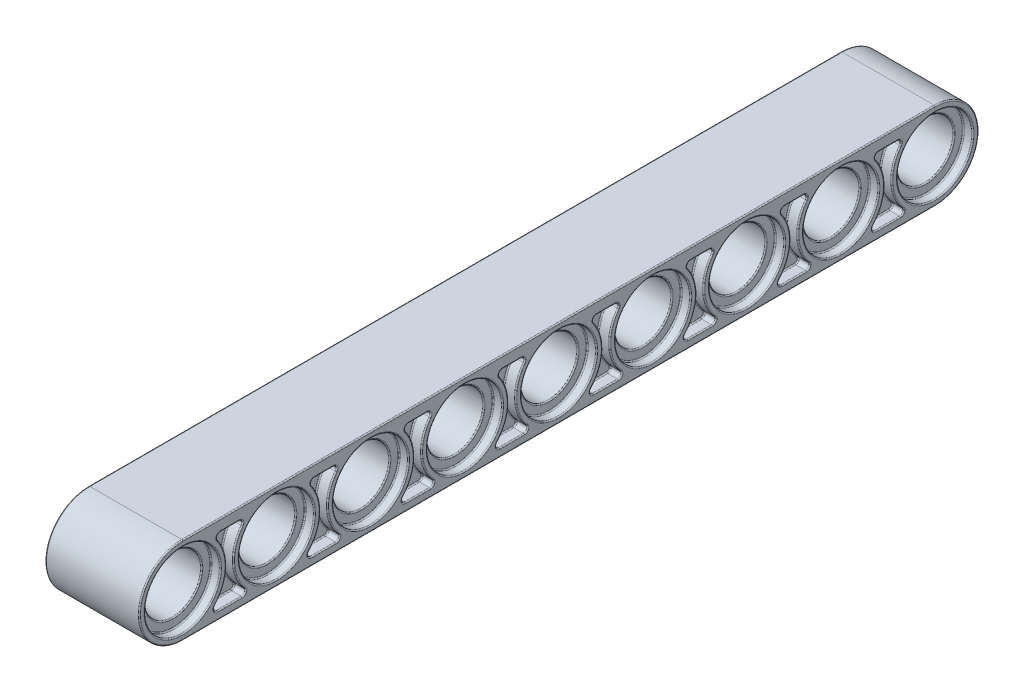
SolidWorks part; units mm, degrees
ref_plane "Front Plane" through (0, 0, 0) normal (0, 0, 1) x (1, 0, 0)
ref_plane "Top Plane" through (0, 0, 0) normal (0, 1, 0) x (1, 0, 0)
ref_plane "Right Plane" through (0, 0, 0) normal (1, 0, 0) x (0, 0, -1)
sketch "Sketch2" plane through (0, 0, 0) normal (1, 0, 0) x (0, 0, -1)
  line L0 (-40.2133, 0) -> (23.7867, 0) construction
  line L1 (-40.2133, 3.7) -> (23.7867, 3.7)
  line L2 (-40.2133, -3.7) -> (23.7867, -3.7)
  arc A0 (-40.2133, 3.7) -> (-40.2133, -3.7) centre (-40.2133, 0) ccw
  arc A1 (23.7867, -3.7) -> (23.7867, 3.7) centre (23.7867, 0) ccw
  circle A2 centre (-40.2133, 0) radius 2.4
  circle A3 centre (-32.2133, 0) radius 2.4
  circle A4 centre (-24.2133, 0) radius 2.4
  circle A5 centre (-16.2133, 0) radius 2.4
  circle A6 centre (-8.2133, 0) radius 2.4
  circle A7 centre (-0.2133, 0) radius 2.4
  circle A8 centre (7.7867, 0) radius 2.4
  circle A9 centre (15.7867, 0) radius 2.4
  circle A10 centre (23.7867, 0) radius 2.4
  point P3 (-8.2133, 0)
  dimension "D2" = 64
  dimension "D3" = 9
  dimension "D1" = 7.4
extrude "Boss-Extrude1" add sketch "Sketch2" along normal blind 8
sketch "Sketch3" plane through (8, 0, 0) normal (1, 0, 0) x (0, 0, -1)
  circle A0 centre (-40.2133, 0) radius 3.2
  circle A1 centre (-32.2133, 0) radius 3.2
  circle A2 centre (-24.2133, 0) radius 3.2
  circle A3 centre (-16.2133, 0) radius 3.2
  circle A4 centre (-8.2133, 0) radius 3.2
  circle A5 centre (-0.2133, 0) radius 3.2
  circle A6 centre (7.7867, 0) radius 3.2
  circle A7 centre (15.7867, 0) radius 3.2
  circle A8 centre (23.7867, 0) radius 3.2
  dimension "D1" = 6.4
  dimension "D2" = 9
extrude "Cut-Extrude1" cut sketch "Sketch3" against normal blind 0.8
ref_plane "Plane1" through (4, 0, 0) normal (1, 0, 0) x (0, 0, -1)
mirror "Mirror1" about plane through (4, 0, 0) normal (1, 0, 0) of "Cut-Extrude1"
sketch "Sketch4" plane through (8, 0, 0) normal (1, 0, 0) x (0, 0, -1)
  line L0 (-37.0133, 2.7) -> (-35.4133, 2.7)
  line L1 (23.7867, 3.7) -> (-40.2133, 3.7) construction
  line L2 (-40.2133, 0) -> (-51.0424, 0) construction
  line L3 (-37.2621, -3) -> (-35.1646, -3)
  line L4 (-29.0133, 2.7) -> (-27.4133, 2.7)
  line L5 (-29.2621, -3) -> (-27.1646, -3)
  line L6 (-21.0133, 2.7) -> (-19.4133, 2.7)
  line L7 (-21.2621, -3) -> (-19.1646, -3)
  line L8 (-13.0133, 2.7) -> (-11.4133, 2.7)
  line L9 (-13.2621, -3) -> (-11.1646, -3)
  line L10 (-5.0133, 2.7) -> (-3.4133, 2.7)
  line L11 (-5.2621, -3) -> (-3.1646, -3)
  line L12 (2.9867, 2.7) -> (4.5867, 2.7)
  line L13 (2.7379, -3) -> (4.8354, -3)
  line L14 (10.9867, 2.7) -> (12.5867, 2.7)
  line L15 (10.7379, -3) -> (12.8354, -3)
  line L16 (18.9867, 2.7) -> (20.5867, 2.7)
  line L17 (18.7379, -3) -> (20.8354, -3)
  line L20 (26.9867, 2.7) -> (28.5867, 2.7) [skipped]
  line L21 (26.7379, -3) -> (28.8354, -3) [skipped]
  arc A0 (-37.4834, -2.4975) -> (-37.2533, 2.22) centre (-40.2133, 0) ccw
  arc A1 (-35.1733, 2.22) -> (-34.9433, -2.4975) centre (-32.2133, 0) ccw
  arc A2 (-37.2621, -3) -> (-37.4834, -2.4975) centre (-37.2621, -2.7) cw
  arc A3 (-34.9433, -2.4975) -> (-35.1646, -3) centre (-35.1646, -2.7) cw
  arc A4 (-35.1733, 2.22) -> (-35.4133, 2.7) centre (-35.4133, 2.4) ccw
  arc A5 (-37.2533, 2.22) -> (-37.0133, 2.7) centre (-37.0133, 2.4) cw
  arc A6 (-29.2533, 2.22) -> (-29.0133, 2.7) centre (-29.0133, 2.4) cw
  arc A7 (-27.1733, 2.22) -> (-27.4133, 2.7) centre (-27.4133, 2.4) ccw
  arc A8 (-27.1733, 2.22) -> (-26.9433, -2.4975) centre (-24.2133, 0) ccw
  arc A9 (-29.4834, -2.4975) -> (-29.2533, 2.22) centre (-32.2133, 0) ccw
  arc A10 (-26.9433, -2.4975) -> (-27.1646, -3) centre (-27.1646, -2.7) cw
  arc A11 (-29.2621, -3) -> (-29.4834, -2.4975) centre (-29.2621, -2.7) cw
  arc A12 (-21.2533, 2.22) -> (-21.0133, 2.7) centre (-21.0133, 2.4) cw
  arc A13 (-19.1733, 2.22) -> (-19.4133, 2.7) centre (-19.4133, 2.4) ccw
  arc A14 (-19.1733, 2.22) -> (-18.9433, -2.4975) centre (-16.2133, 0) ccw
  arc A15 (-21.4834, -2.4975) -> (-21.2533, 2.22) centre (-24.2133, 0) ccw
  arc A16 (-18.9433, -2.4975) -> (-19.1646, -3) centre (-19.1646, -2.7) cw
  arc A17 (-21.2621, -3) -> (-21.4834, -2.4975) centre (-21.2621, -2.7) cw
  arc A18 (-13.2533, 2.22) -> (-13.0133, 2.7) centre (-13.0133, 2.4) cw
  arc A19 (-11.1733, 2.22) -> (-11.4133, 2.7) centre (-11.4133, 2.4) ccw
  arc A20 (-11.1733, 2.22) -> (-10.9433, -2.4975) centre (-8.2133, 0) ccw
  arc A21 (-13.4834, -2.4975) -> (-13.2533, 2.22) centre (-16.2133, 0) ccw
  arc A22 (-10.9433, -2.4975) -> (-11.1646, -3) centre (-11.1646, -2.7) cw
  arc A23 (-13.2621, -3) -> (-13.4834, -2.4975) centre (-13.2621, -2.7) cw
  arc A24 (-5.2533, 2.22) -> (-5.0133, 2.7) centre (-5.0133, 2.4) cw
  arc A25 (-3.1733, 2.22) -> (-3.4133, 2.7) centre (-3.4133, 2.4) ccw
  arc A26 (-3.1733, 2.22) -> (-2.9433, -2.4975) centre (-0.2133, 0) ccw
  arc A27 (-5.4834, -2.4975) -> (-5.2533, 2.22) centre (-8.2133, 0) ccw
  arc A28 (-2.9433, -2.4975) -> (-3.1646, -3) centre (-3.1646, -2.7) cw
  arc A29 (-5.2621, -3) -> (-5.4834, -2.4975) centre (-5.2621, -2.7) cw
  arc A30 (2.7467, 2.22) -> (2.9867, 2.7) centre (2.9867, 2.4) cw
  arc A31 (4.8267, 2.22) -> (4.5867, 2.7) centre (4.5867, 2.4) ccw
  arc A32 (4.8267, 2.22) -> (5.0567, -2.4975) centre (7.7867, 0) ccw
  arc A33 (2.5166, -2.4975) -> (2.7467, 2.22) centre (-0.2133, 0) ccw
  arc A34 (5.0567, -2.4975) -> (4.8354, -3) centre (4.8354, -2.7) cw
  arc A35 (2.7379, -3) -> (2.5166, -2.4975) centre (2.7379, -2.7) cw
  arc A36 (10.7467, 2.22) -> (10.9867, 2.7) centre (10.9867, 2.4) cw
  arc A37 (12.8267, 2.22) -> (12.5867, 2.7) centre (12.5867, 2.4) ccw
  arc A38 (12.8267, 2.22) -> (13.0567, -2.4975) centre (15.7867, 0) ccw
  arc A39 (10.5166, -2.4975) -> (10.7467, 2.22) centre (7.7867, 0) ccw
  arc A40 (13.0567, -2.4975) -> (12.8354, -3) centre (12.8354, -2.7) cw
  arc A41 (10.7379, -3) -> (10.5166, -2.4975) centre (10.7379, -2.7) cw
  arc A42 (18.7467, 2.22) -> (18.9867, 2.7) centre (18.9867, 2.4) cw
  arc A43 (20.8267, 2.22) -> (20.5867, 2.7) centre (20.5867, 2.4) ccw
  arc A44 (20.8267, 2.22) -> (21.0567, -2.4975) centre (23.7867, 0) ccw
  arc A45 (18.5166, -2.4975) -> (18.7467, 2.22) centre (15.7867, 0) ccw
  arc A46 (21.0567, -2.4975) -> (20.8354, -3) centre (20.8354, -2.7) cw
  arc A47 (18.7379, -3) -> (18.5166, -2.4975) centre (18.7379, -2.7) cw
  arc A54 (28.8267, 2.22) -> (29.0567, -2.4975) centre (31.7867, 0) ccw [skipped]
  arc A55 (28.8267, 2.22) -> (28.5867, 2.7) centre (28.5867, 2.4) ccw [skipped]
  arc A56 (26.7467, 2.22) -> (26.9867, 2.7) centre (26.9867, 2.4) cw [skipped]
  arc A57 (26.5166, -2.4975) -> (26.7467, 2.22) centre (23.7867, 0) ccw [skipped]
  arc A58 (29.0567, -2.4975) -> (28.8354, -3) centre (28.8354, -2.7) cw [skipped]
  arc A59 (26.7379, -3) -> (26.5166, -2.4975) centre (26.7379, -2.7) cw [skipped]
  dimension "D1" = 2
  dimension "D3" = 0.3
  dimension "D2" = 1
  dimension "D4" = 9
extrude "Cut-Extrude2" cut sketch "Sketch4" against normal blind 1
mirror "Mirror2" about plane through (4, 0, 0) normal (1, 0, 0) of "Cut-Extrude2"
fillet "Fillet1" radius 0.1 318 edges at (7.2, 0, -26.9867) (7, -0.1802, -19.4823) (7, 2.5342, -18.7183) (7, 2.7, -19.7867) (7, 2.5342, -20.855) (7, -0.1802, -20.0911) (7, -2.8209, -21.1099) (7, -3, -19.7867) (7, -2.8209, -18.4634) (7.2, 0, -18.9867) (7, -0.1802, -11.4823) (7, 2.5342, -10.7183) (7, 2.7, -11.7867) (7, 2.5342, -12.855) (7, -0.1802, -12.0911) (7, -2.8209, -13.1099) (7, -3, -11.7867) (7, -2.8209, -10.4634) (7.2, 0, -10.9867) (7, -0.1802, -3.4823) (7, 2.5342, -2.7183) (7, 2.7, -3.7867) (7, 2.5342, -4.855) (7, -0.1802, -4.0911) (7, -2.8209, -5.1099) (7, -3, -3.7867) (7, -2.8209, -2.4634) (7.2, 0, -2.9867) (7, -0.1802, 4.5177) (7, 2.5342, 5.2817) (7, 2.7, 4.2133) (7, 2.5342, 3.145) (7, -0.1802, 3.9089) (7, -2.8209, 2.8901) (7, -3, 4.2133) (7, -2.8209, 5.5366) (7.2, 0, 5.0133) (7, -0.1802, 12.5177) (7, 2.5342, 13.2817) (7, 2.7, 12.2133) (7, 2.5342, 11.145) (7, -0.1802, 11.9089) (7, -2.8209, 10.8901) (7, -3, 12.2133) (7, -2.8209, 13.5366) (7.2, 0, 13.0133) (7, -0.1802, 20.5177) (7, 2.5342, 21.2817) (7, 2.7, 20.2133) (7, 2.5342, 19.145) (7, -0.1802, 19.9089) (7, -2.8209, 18.8901) (7, -3, 20.2133) (7, -2.8209, 21.5366) (7.2, 0, 21.0133) (7.2, 0, 29.0133) (7, -0.1802, 28.5177) (7, 2.5342, 29.2817) (7, 2.7, 28.2133) (7, 2.5342, 27.145) (7, -0.1802, 27.9089) (7, -2.8209, 26.8901) (7, -3, 28.2133) (7, -2.8209, 29.5366) (7, -0.1802, 36.5177) (7, 2.5342, 37.2817) (7, 2.7, 36.2133) (7, 2.5342, 35.145) (7, -0.1802, 35.9089) (7, -2.8209, 34.8901) (7, -3, 36.2133) (7, -2.8209, 37.5366) (7.2, 0, 37.0133) (7.2, 0, 37.8133) (0.8, 0, 37.0133) (0.8, 0, 42.6133) (1, -3, 36.2133) (1, -2.8209, 34.8901) (1, -0.1802, 35.9089) (1, 2.5342, 35.145) (1, 2.7, 36.2133) (1, 2.5342, 37.2817) (1, -0.1802, 36.5177) (1, -2.8209, 37.5366) (0.8, 0, 26.6133) (7.2, 0, 21.8133) (7.2, 0, 29.8133) (0.8, 0, 29.0133) (0.8, 0, 34.6133) (1, -3, 28.2133) (1, -2.8209, 26.8901) (1, -0.1802, 27.9089) (1, 2.5342, 27.145) (1, 2.7, 28.2133) (1, 2.5342, 29.2817) (1, -0.1802, 28.5177) (1, -2.8209, 29.5366) (0.8, 0, 21.0133) (1, -3, 20.2133) (1, -2.8209, 18.8901) (1, -0.1802, 19.9089) (1, 2.5342, 19.145) (1, 2.7, 20.2133) (1, 2.5342, 21.2817) (1, -0.1802, 20.5177) (1, -2.8209, 21.5366) (7.2, 0, 13.8133) (0.8, 0, 13.0133) (0.8, 0, 18.6133) (1, -3, 12.2133) (1, -2.8209, 10.8901) (1, -0.1802, 11.9089) (1, 2.5342, 11.145) (1, 2.7, 12.2133) (1, 2.5342, 13.2817) (1, -0.1802, 12.5177) (1, -2.8209, 13.5366) (0.8, 0, 5.0133) (0.8, 0, 10.6133) (7.2, 0, 5.8133) (1, -3, 4.2133) (1, -2.8209, 2.8901) (1, -0.1802, 3.9089) (1, 2.5342, 3.145) (1, 2.7, 4.2133) (1, 2.5342, 5.2817) (1, -0.1802, 4.5177) (1, -2.8209, 5.5366) (7.2, 0, -2.1867) (0.8, 0, -2.9867) (0.8, 0, 2.6133) (1, -3, -3.7867) (1, -2.8209, -5.1099) (1, -0.1802, -4.0911) (1, 2.5342, -4.855) (1, 2.7, -3.7867) (1, 2.5342, -2.7183) (1, -0.1802, -3.4823) (1, -2.8209, -2.4634) (7.2, 0, -10.1867) (0.8, 0, -10.9867) (0.8, 0, -5.3867) (1, -3, -11.7867) (1, -2.8209, -13.1099) (1, -0.1802, -12.0911) (1, 2.5342, -12.855) (1, 2.7, -11.7867) (1, 2.5342, -10.7183) (1, -0.1802, -11.4823) (1, -2.8209, -10.4634) (7.2, 0, -18.1867) (0.8, 0, -18.9867) (0.8, 0, -13.3867) (1, -3, -19.7867) (1, -2.8209, -21.1099) (1, -0.1802, -20.0911) (1, 2.5342, -20.855) (1, 2.7, -19.7867) (1, 2.5342, -18.7183) (1, -0.1802, -19.4823) (1, -2.8209, -18.4634) (0.8, 0, -26.9867) (0.8, 0, -21.3867) (7.2, 0, -26.1867) (0, -3.7, 8.2133) (0, 0, -27.4867) (0, -0.1802, -11.4823) (0, 2.5342, -10.7183) (0, 2.7, -11.7867) (0, 2.5342, -12.855) (0, -0.1802, -12.0911) (0, -2.8209, -13.1099) (0, -3, -11.7867) (0, -2.8209, -10.4634) (0, -0.1802, 4.5177) (0, 2.5342, 5.2817) (0, 2.7, 4.2133) (0, 2.5342, 3.145) (0, -0.1802, 3.9089) (0, -2.8209, 2.8901) (0, -3, 4.2133) (0, -2.8209, 5.5366) (0, -0.1802, 20.5177) (0, 2.5342, 21.2817) (0, 2.7, 20.2133) (0, 2.5342, 19.145) (0, -0.1802, 19.9089) (0, -2.8209, 18.8901) (0, -3, 20.2133) (0, -2.8209, 21.5366) (0, -0.1802, 36.5177) (0, 2.5342, 37.2817) (0, 2.7, 36.2133) (0, 2.5342, 35.145) (0, -0.1802, 35.9089) (0, -2.8209, 34.8901) (0, -3, 36.2133) (0, -2.8209, 37.5366) (0, 0, -18.9867) (0, 0, -2.9867) (0, 0, 13.0133) (0, 0, 29.0133) (0, 0, 37.0133) (0, 0, 21.0133) (0, 0, 5.0133) (0, 0, -10.9867) (0, 0, -26.9867) (0, -0.1802, 28.5177) (0, 2.5342, 29.2817) (0, 2.7, 28.2133) (0, 2.5342, 27.145) (0, -0.1802, 27.9089) (0, -2.8209, 26.8901) (0, -3, 28.2133) (0, -2.8209, 29.5366) (0, -0.1802, 12.5177) (0, 2.5342, 13.2817) (0, 2.7, 12.2133) (0, 2.5342, 11.145) (0, -0.1802, 11.9089) (0, -2.8209, 10.8901) (0, -3, 12.2133) (0, -2.8209, 13.5366) (0, -0.1802, -3.4823) (0, 2.5342, -2.7183) (0, 2.7, -3.7867) (0, 2.5342, -4.855) (0, -0.1802, -4.0911) (0, -2.8209, -5.1099) (0, -3, -3.7867) (0, -2.8209, -2.4634) (0, -0.1802, -19.4823) (0, 2.5342, -18.7183) (0, 2.7, -19.7867) (0, 2.5342, -20.855) (0, -0.1802, -20.0911) (0, -2.8209, -21.1099) (0, -3, -19.7867) (0, -2.8209, -18.4634) (0, 3.7, 8.2133) (0, 0, 43.9133) (8, 0, 37.0133) (8, 0, 29.0133) (8, 0, 21.0133) (8, 0, 13.0133) (8, 0, 5.0133) (8, 0, -2.9867) (8, 0, -10.9867) (8, 0, -18.9867) (8, 0, -26.9867) (8, -3, 36.2133) (8, -2.8209, 34.8901) (8, -0.1802, 35.9089) (8, 2.5342, 35.145) (8, 2.7, 36.2133) (8, 2.5342, 37.2817) (8, -0.1802, 36.5177) (8, -2.8209, 37.5366) (8, -3, 28.2133) (8, -2.8209, 26.8901) (8, -0.1802, 27.9089) (8, 2.5342, 27.145) (8, 2.7, 28.2133) (8, 2.5342, 29.2817) (8, -0.1802, 28.5177) (8, -2.8209, 29.5366) (8, -3, 20.2133) (8, -2.8209, 18.8901) (8, -0.1802, 19.9089) (8, 2.5342, 19.145) (8, 2.7, 20.2133) (8, 2.5342, 21.2817) (8, -0.1802, 20.5177) (8, -2.8209, 21.5366) (8, -3, 12.2133) (8, -2.8209, 10.8901) (8, -0.1802, 11.9089) (8, 2.5342, 11.145) (8, 2.7, 12.2133) (8, 2.5342, 13.2817) (8, -0.1802, 12.5177) (8, -2.8209, 13.5366) (8, -3, 4.2133) (8, -2.8209, 2.8901) (8, -0.1802, 3.9089) (8, 2.5342, 3.145) (8, 2.7, 4.2133) (8, 2.5342, 5.2817) (8, -0.1802, 4.5177) (8, -2.8209, 5.5366) (8, -3, -3.7867) (8, -2.8209, -5.1099) (8, -0.1802, -4.0911) (8, 2.5342, -4.855) (8, 2.7, -3.7867) (8, 2.5342, -2.7183) (8, -0.1802, -3.4823) (8, -2.8209, -2.4634) (8, -3, -11.7867) (8, -2.8209, -13.1099) (8, -0.1802, -12.0911) (8, 2.5342, -12.855) (8, 2.7, -11.7867) (8, 2.5342, -10.7183) (8, -0.1802, -11.4823) (8, -2.8209, -10.4634) (8, -3, -19.7867) (8, -2.8209, -21.1099) (8, -0.1802, -20.0911) (8, 2.5342, -20.855) (8, 2.7, -19.7867) (8, 2.5342, -18.7183) (8, -0.1802, -19.4823) (8, -2.8209, -18.4634) (8, -3.7, 8.2133) (8, 0, 43.9133) (8, 3.7, 8.2133) (8, 0, -27.4867)
